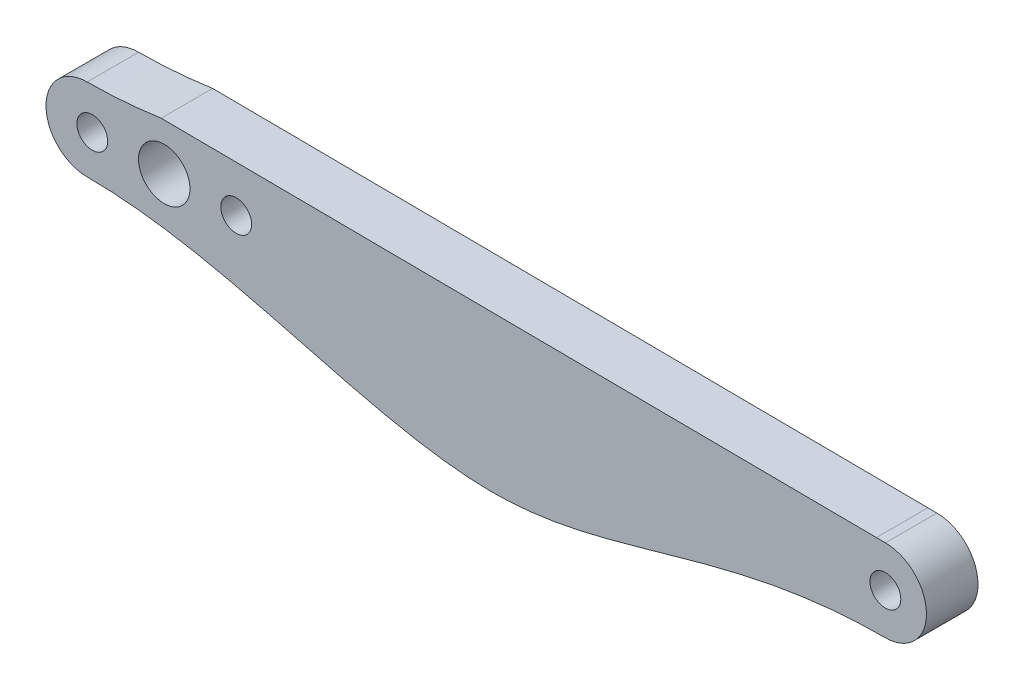
SolidWorks part; units mm, degrees
ref_plane "Front Plane" through (0, 0, 0) normal (0, 0, 1) x (1, 0, 0)
ref_plane "Top Plane" through (0, 0, 0) normal (0, 1, 0) x (1, 0, 0)
ref_plane "Right Plane" through (0, 0, 0) normal (1, 0, 0) x (0, 0, -1)
sketch "Sketch1" plane through (0, 0, 0) normal (0, 0, 1) x (1, 0, 0)
  line L0 (0, 0) -> (-70.14, 0) construction
  line L1 (0, -4) -> (-70.14, -4)
  line L2 (0, 4) -> (-70.14, 4)
  arc A0 (0, -4) -> (0, 4) centre (0, 0) ccw
  arc A1 (-70.14, 4) -> (-70.14, -4) centre (-70.14, 0) ccw
  circle A2 centre (-70.14, 0) radius 1.5
  circle A3 centre (0, 0) radius 1.5
  point P3 (-35.07, 0)
  dimension "D3" = 3
  dimension "D4" = 3
  dimension "D1" = 70.14
  dimension "D2" = 8
extrude "Boss-Extrude1" add sketch "Sketch1" along normal blind 5
sketch "Sketch2" plane through (0, 0, 5) normal (0, 0, 1) x (1, 0, 0)
  line L0 (-67.4585, 0) -> (-76.1432, 0) construction
  line L1 (-70.14, 0) -> (-77.64, 0) construction
  line L2 (-70.14, -4) -> (-77.64, -4)
  line L3 (-70.14, 4) -> (-77.64, 4)
  arc A0 (-70.14, -4) -> (-70.14, 4) centre (-70.14, 0) ccw
  arc A1 (-77.64, 4) -> (-77.64, -4) centre (-77.64, 0) ccw
  circle A2 centre (-77.64, 0) radius 1.35
  circle A3 centre (-62.64, 0) radius 1.35
  point P6 (-73.89, 0)
  dimension "D3" = 2.7
  dimension "D5" = 2.7
  dimension "D1" = 7.5
  dimension "D2" = 8
  dimension "D4" = 15
sketch "Sketch3" plane through (0, 0, 0) normal (0, 0, 1) x (1, 0, 0)
  line L0 (-70.14, 0) -> (-77.64, 0) construction
  line L1 (-70.14, -4) -> (-77.64, -4)
  line L2 (-70.14, 4) -> (-77.64, 4)
  arc A0 (-70.14, -4) -> (-70.14, 4) centre (-70.14, 0) ccw
  arc A1 (-77.64, 4) -> (-77.64, -4) centre (-77.64, 0) ccw
  circle A2 centre (-70.14, 0) radius 1.5
  point P4 (-73.89, 0)
  dimension "D2" = 3
  dimension "D1" = 8
extrude "Boss-Extrude3" add sketch "Sketch3" along normal blind 5 contours L2 A1 L1 A0
sketch "Sketch4" plane through (0, 0, 0) normal (0, 0, -1) x (-1, 0, 0)
  circle A2 centre (70.14, 0) radius 2.5
  dimension "5" = 5
extrude "Cut-Extrude2" cut sketch "Sketch4" against normal blind 5
sketch "Sketch5" plane through (0, 0, 5) normal (0, 0, 1) x (1, 0, 0)
  line L0 (-77.64, 0) -> (-67.4585, 0) construction
  line L2 (-84.4893, -21.6503) -> (6.9893, -21.6503)
  line L3 (-84.4893, -21.6503) -> (-84.4893, 18.2006)
  line L4 (-84.4893, 18.2006) -> (6.9893, 18.2006)
  line L5 (6.9893, -21.6503) -> (6.9893, 18.2006)
  arc A0 (-77.64, 4) -> (-77.64, -4) centre (-77.64, 0) ccw construction
  arc A1 (0, -4) -> (0, 4) centre (0, 0) ccw construction
  spline S0 degree 3 poles (-77.64, -4) (-63.5276, -4) (-37.042, -17.7091) (-15.8205, -4) (0, -4) knots 0 0 0 0 0.514247 1 1 1 1
  spline S1 degree 3 poles (-77.64, 4) (-63.5276, 4) (-37.042, 17.7091) (-15.8205, 4) (0, 4) knots 0 0 0 0 0.514247 1 1 1 1
  line M10 (-77.64, -4) -> (0, -4)
  line M12 (0, 4) -> (-77.64, 4)
extrude "Boss-Extrude4" add sketch "Sketch5" against normal blind 5 separate body contours S0 M10 | S1 M12 region at (-39.0172, -6.5182, 5) region at (-39.0172, 6.5182, 5)
sketch "Sketch7" plane through (0, 0, 5) normal (0, 0, 1) x (1, 0, 0)
  line L0 (-77.64, 4) -> (0, 4) construction
  line L1 (-77.64, -4) -> (0, -4) construction
  line L2 (0, 4) -> (-77.64, 4) construction
  line L3 (0, -4) -> (-77.64, -4) construction
  line L4 (-77.64, 4) -> (0, 4)
  line L5 (-77.64, -4) -> (0, -4)
  line L6 (0, 4) -> (-77.64, 4)
  line L7 (0, -4) -> (-77.64, -4)
  arc A0 (-77.64, 4) -> (-77.64, -4) centre (-77.64, 0) ccw construction
  arc A1 (0, -4) -> (0, 4) centre (0, 0) ccw construction
  arc A2 (-77.64, 4) -> (-77.64, -4) centre (-77.64, 0) ccw
  arc A3 (0, -4) -> (0, 4) centre (0, 0) ccw
  spline S0 degree 3 poles (1172.9519, 1619.4509) (51.942, -188.0031) (-2.5143, 227.5373) (-223.6856, -225.2512) (-215.6991, 1995.286) knots -2.193099 -2.193099 -2.193099 -2.193099 0.485753 3.434502 3.434502 3.434502 3.434502 only from (0, 4) to (-77.64, 4) construction
  spline S1 degree 3 poles (-215.6988, -1995.3643) (-223.6883, 225.2567) (-2.5159, -227.5372) (51.9414, 187.9983) (1172.9116, -1619.3859) knots -2.434537 -2.434537 -2.434537 -2.434537 0.514247 3.193066 3.193066 3.193066 3.193066 only from (-77.64, -4) to (0, -4) construction
  spline S2 degree 3 poles (0, 4) (-15.8205, 4) (-37.042, 17.7091) (-63.5276, 4) (-77.64, 4) knots 0 0 0 0 0.485753 1 1 1 1
  spline S3 degree 3 poles (-77.64, -4) (-63.5276, -4) (-37.042, -17.7091) (-15.8205, -4) (0, -4) knots 0 0 0 0 0.514247 1 1 1 1
  circle M3 centre (-70.14, 0) radius 2.5
  arc M4 (-77.64, 4) -> (-77.64, -4) centre (-77.64, 0) ccw
  line M5 (-77.64, -4) -> (0, -4)
  arc M6 (0, -4) -> (0, 4) centre (0, 0) ccw
  line M7 (0, 4) -> (-77.64, 4)
  circle M8 centre (0, 0) radius 1.5
extrude "Boss-Extrude5" add sketch "Sketch7" along normal blind 0.01 contours S3 M5 | M7 M4 M5 M6 M8 M3 | S2 M7 region at (-39.0172, 6.5182, 5) region at (-38.2917, 0, 5) region at (-39.0172, -6.5182, 5)
sketch "Sketch9" plane through (0, 0, 5.01) normal (0, 0, 1) x (1, 0, 0)
  line L0 (-70.4405, 4.548) -> (0, 4)
  circle A0 centre (-70.14, 0) radius 4.5455
  arc A3 (0, -4) -> (0, 4) centre (0, 0) ccw
  arc A4 (-77.64, 4) -> (-77.64, -4) centre (-77.64, 0) ccw
  arc A5 (0, -4) -> (0, 4) centre (0, 0) ccw
  arc A6 (-77.64, 4) -> (-77.64, -4) centre (-77.64, 0) ccw
  spline S0 degree 3 poles (-77.64, -4) (-63.5276, -4) (-37.042, -17.7091) (-15.8205, -4) (0, -4) knots 0 0 0 0 0.514247 1 1 1 1 construction
  spline S1 degree 3 poles (0, 4) (-15.8205, 4) (-37.042, 17.7091) (-63.5276, 4) (-77.64, 4) knots 0 0 0 0 0.485753 1 1 1 1 construction
  spline S4 degree 3 poles (-205.8804, -2995.2476) (-254.6859, 291.1761) (8.8112, -289.0605) (58.2905, 245.4062) (1693.5602, -2473.0713) knots -2.818996 -2.818996 -2.818996 -2.818996 0.514247 3.557188 3.557188 3.557188 3.557188 only from (-77.64, -4) to (0, -4)
  spline S5 degree 3 poles (1693.6169, 2473.1655) (58.2911, -245.412) (8.8129, 289.0615) (-254.6837, -291.1712) (-205.8816, 2995.1677) knots -2.557223 -2.557223 -2.557223 -2.557223 0.485753 3.818968 3.818968 3.818968 3.818968 only from (0, 4) to (-77.64, 4)
  spline S6 degree 3 poles (-77.64, -4) (-63.5276, -4) (-37.042, -17.7091) (-15.8205, -4) (0, -4) knots 0 0 0 0 0.514247 1 1 1 1
  spline S7 degree 3 poles (0, 4) (-15.8205, 4) (-37.042, 17.7091) (-63.5276, 4) (-77.64, 4) knots 0 0 0 0 0.485753 1 1 1 1
  spline M9 degree 3 poles (0, 4) (-15.8205, 4) (-37.042, 17.7091) (-63.5276, 4) (-77.64, 4) knots 0 0 0 0 0.485753 1 1 1 1
  dimension "D1" = 0
extrude "Cut-Extrude3" cut sketch "Sketch9" against normal blind 10 contours L0 M9 region at (-38.1293, 6.7155, 5.01)
sketch "Sketch10" plane through (0, 0, 5.01) normal (0, 0, 1) x (1, 0, 0)
  line L0 (-77.14, 0) -> (-63.14, 0)
  circle A0 centre (-77.14, 0) radius 1.5
  circle A1 centre (-63.14, 0) radius 1.5
  circle A2 centre (-70.14, 0) radius 2.5 construction
  dimension "D1" = 7
  dimension "D2" = 3
  dimension "D3" = 7
  dimension "D4" = 3
extrude "Cut-Extrude4" cut sketch "Sketch10" against normal blind 10 contours A0 | A1 region at (-63.14, 1.4576, 5.01) region at (-78.5976, 0, 5.01)
